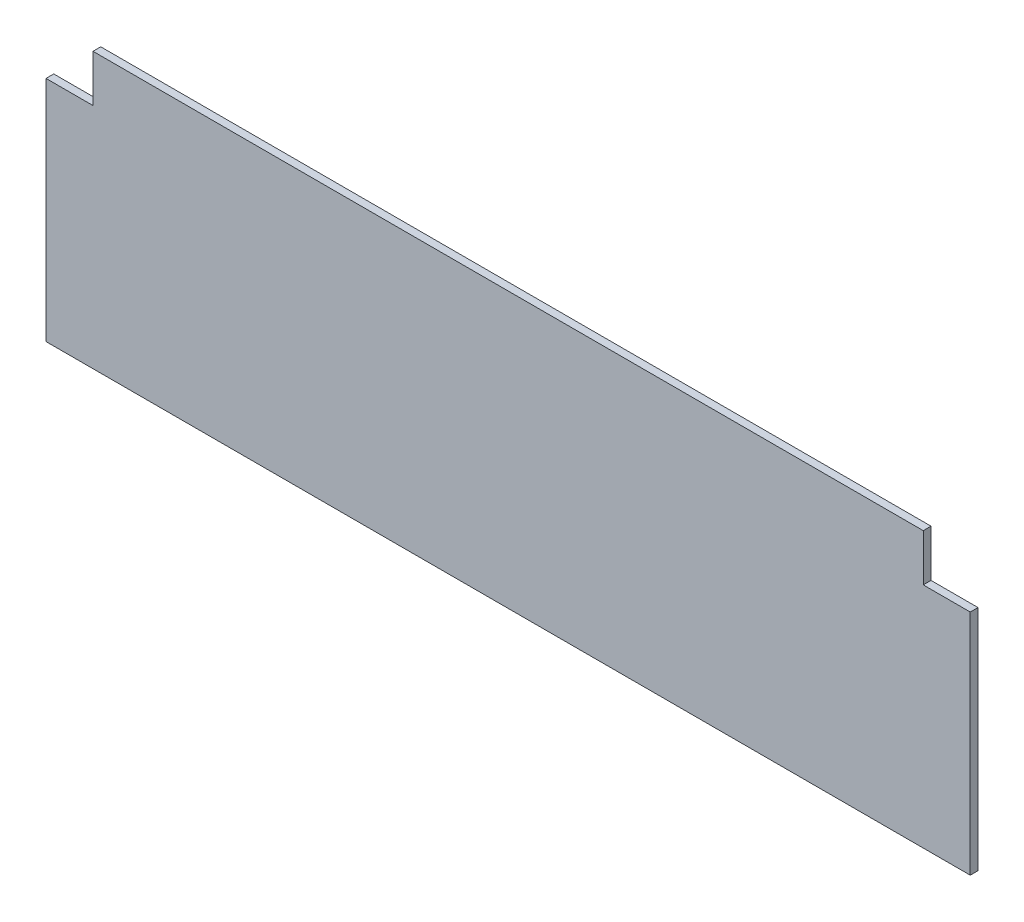
SolidWorks part; units mm, degrees
ref_plane "Front Plane" through (0, 0, 0) normal (0, 0, 1) x (1, 0, 0)
ref_plane "Top Plane" through (0, 0, 0) normal (0, 1, 0) x (1, 0, 0)
ref_plane "Right Plane" through (0, 0, 0) normal (1, 0, 0) x (0, 0, -1)
sketch "Sketch1" plane through (0, 0, 0) normal (0, 0, 1) x (1, 0, 0)
  line L0 (393.4, -136.8219) -> (393.4, -39.8043)
  line L1 (393.4, -39.8043) -> (0, -39.8043) construction
  line L2 (0, -39.8043) -> (0, -136.8219)
  line L3 (0, -136.8219) -> (393.4, -136.8219)
  line L4 (0, -138.3774) -> (0, -39.8043) construction
  line L5 (373.4, -39.8043) -> (20, -39.8043) construction
  line L6 (373.4, -39.8043) -> (373.4, -19.8043)
  line L7 (373.4, -19.8043) -> (20, -19.8043)
  line L8 (20, -39.8043) -> (20, -19.8043)
  line L9 (373.4, -39.8043) -> (20, -19.8043) construction
  line L10 (373.4, -19.8043) -> (20, -39.8043) construction
  line L13 (20.7, -19.8043) -> (372.7, -19.8043) construction
  line L14 (393.4, -39.8043) -> (393.4, -138.3812) construction
  line L18 (0, -136.8219) -> (393.4, -136.8219) construction
  line L19 (393.4, -39.8043) -> (373.4, -39.8043)
  line L20 (0, -39.8043) -> (20, -39.8043)
  point P12 (196.7, -29.8043)
  dimension "D1" = 20
  dimension "D2" = 20
  dimension "D3" = 20
extrude "Boss-Extrude1" add sketch "Sketch1" against normal blind 3.3 contours L2 L3 L0 L1 | L8 L1 L6 L7 region at (196.7, -79.171, 0)
